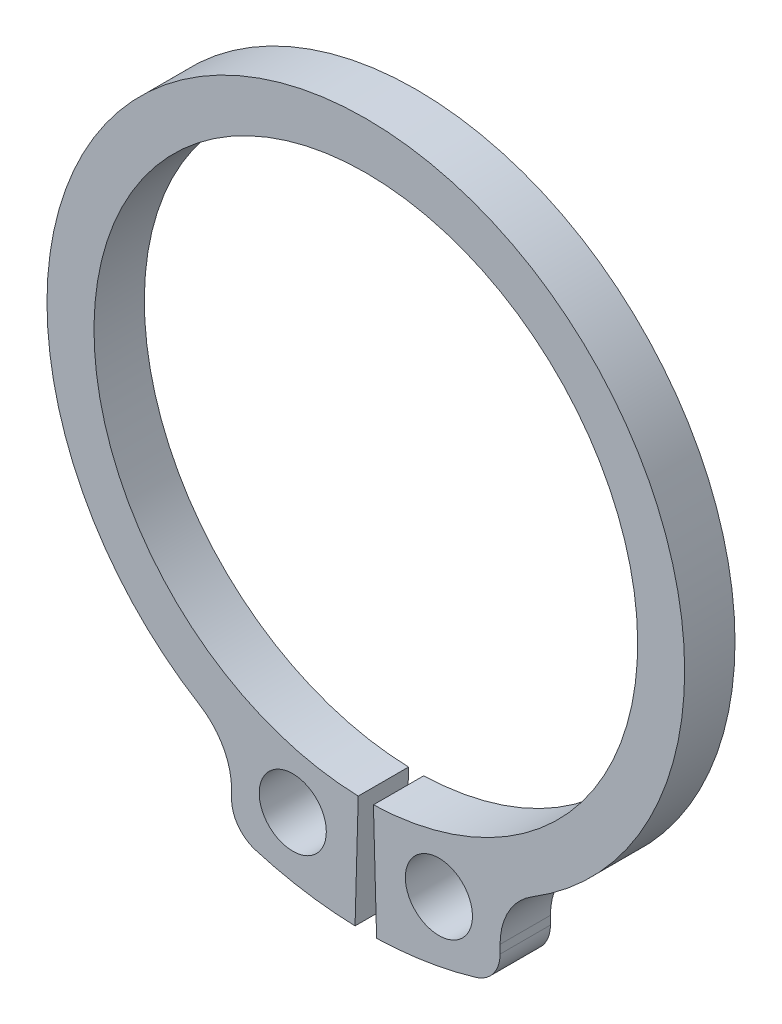
SolidWorks part; units mm, degrees
ref_plane "Спереди" through (0, 0, 0) normal (0, 0, 1) x (1, 0, 0)
ref_plane "Сверху" through (0, 0, 0) normal (0, 1, 0) x (1, 0, 0)
ref_plane "Справа" through (0, 0, 0) normal (1, 0, 0) x (0, 0, -1)
sketch "Эскиз1" plane through (0, 0, 0) normal (0, 0, 1) x (1, 0, 0)
  line L0 (0, -9.6776) -> (0, 50000) construction
  line L1 (0, 0) -> (-0.1961, -7.0212) construction
  line L2 (-0.3211, -11.4955) -> (-0.2262, -8.0968)
  line L3 (-0.2262, -8.0968) -> (-0.8681, -31.0788) construction
  line L4 (-4, -10.0623) -> (-4, -9.8107)
  line L5 (4, -10.0623) -> (4, -9.8107)
  line L6 (0.3211, -11.4955) -> (0.2262, -8.0968)
  arc A0 (0.2262, -8.0968) -> (-0.2262, -8.0968) centre (0, 0) ccw
  circle A2 centre (0, 0) radius 12 construction
  circle A3 centre (0, 0) radius 8.5 construction
  arc A4 (-3.2857, -11.0206) -> (-0.3211, -11.4955) centre (0, 0) ccw
  arc A5 (-4, -9.8107) -> (-4.9565, -8.1045) centre (-6, -9.8107) ccw
  arc A6 (-3.2857, -11.0206) -> (-4, -10.0623) centre (-3, -10.0623) cw
  arc A7 (3.2857, -11.0206) -> (4, -10.0623) centre (3, -10.0623) ccw
  arc A8 (4, -9.8107) -> (4.9565, -8.1045) centre (6, -9.8107) cw
  arc A9 (0.3211, -11.4955) -> (3.2857, -11.0206) centre (0, 0) ccw
  arc A10 (4.9565, -8.1045) -> (-4.9565, -8.1045) centre (0, 0) ccw
  circle A11 centre (-2.0907, -9.6776) radius 0.996
  circle A12 centre (2.0907, -9.6776) radius 0.996
  point P15 (-1.8097, -9.8107)
  point P26 (-2.0907, -9.6776)
  dimension "D1" = 16.2
  dimension "D3" = 24
  dimension "D4" = 17
  dimension "D6" = 23
  dimension "D8" = 2
  dimension "D9" = 1
  dimension "D5" = 1.6
  dimension "D7" = 8
extrude "Бобышка-Вытянуть1" add sketch "Эскиз1" along normal blind 1.5 contours A10 A5 L4 A6 A4 L2 A0 L6 A9 A7 L5 A8
sketch "Эскиз2" plane through (0, 0, 0) normal (0, 0, -1) x (-1, 0, 0)
  line L0 (0, 0) -> (0, -23.8017) construction
  circle A0 centre (-2.177, -9.4946) radius 1
  circle A1 centre (2.177, -9.4946) radius 1
  dimension "D1" = 2
extrude "Вырез-Вытянуть1" cut sketch "Эскиз2" against normal blind 1.5
